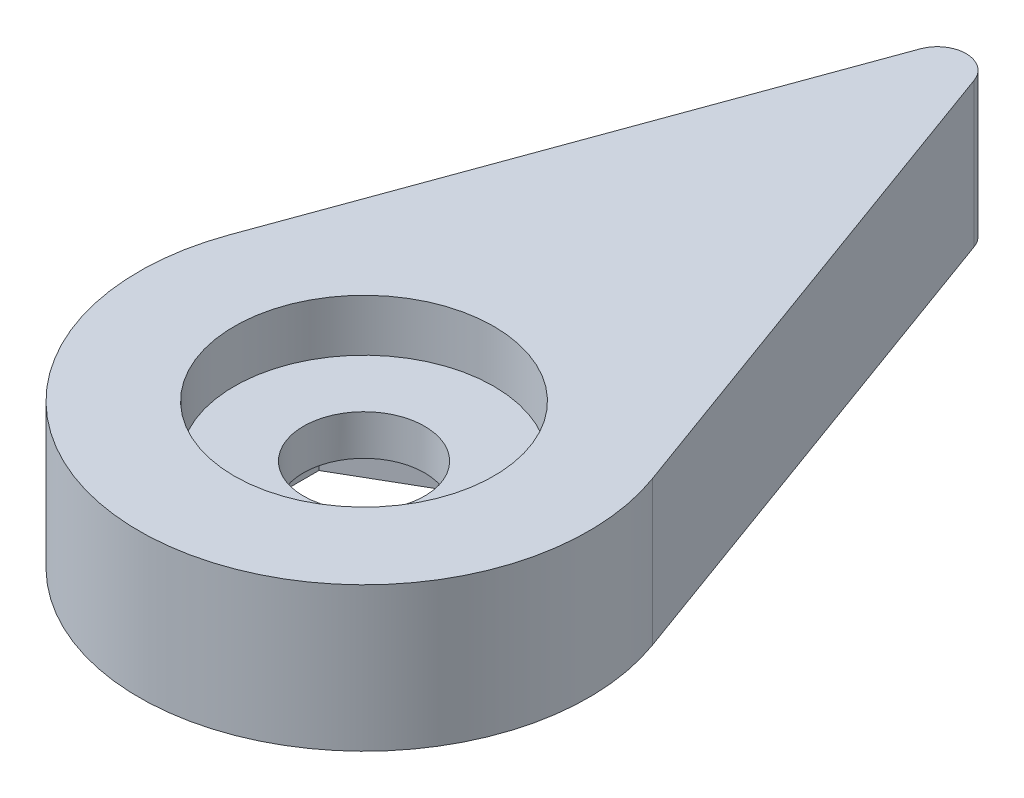
SolidWorks part; units mm, degrees
ref_plane "Front Plane" through (0, 0, 0) normal (0, 0, 1) x (1, 0, 0)
ref_plane "Top Plane" through (0, 0, 0) normal (0, 1, 0) x (1, 0, 0)
ref_plane "Right Plane" through (0, 0, 0) normal (1, 0, 0) x (0, 0, -1)
sketch "Sketch1" plane through (0, 0, 0) normal (0, 1, 0) x (1, 0, 0)
  line L3 (0, -55) -> (0, 55) construction
  line L12 (-0.9397, 20.2239) -> (-7.3296, 2.6678)
  line L15 (7.3296, 2.6678) -> (0.9397, 20.2239)
  arc A0 (-7.3296, 2.6678) -> (7.3296, 2.6678) centre (0, 0) ccw
  arc A12 (0.9397, 20.2239) -> (-0.9397, 20.2239) centre (0, 19.8819) ccw
  dimension "D1" = 7.8
  dimension "D3" = 1
  dimension "D5" = 40
extrude "Boss-Extrude2" add sketch "Sketch1" along normal blind 5
sketch "Sketch3" plane through (0, 5, 0) normal (0, 1, 0) x (1, 0, 0)
  circle A0 centre (0, 0) radius 2.1
  dimension "D1" = 4.2
extrude "Cut-Extrude1" cut sketch "Sketch3" against normal up to next
sketch "Sketch4" plane through (0, 5, 0) normal (0, 1, 0) x (1, 0, 0)
  circle A1 centre (0, 0) radius 4.5
  dimension "D1" = 9
extrude "Cut-Extrude2" cut sketch "Sketch4" against normal blind 1.8
sketch "Sketch5" plane through (0, 0, 0) normal (0, -1, 0) x (1, 0, 0)
  line L0 (0, -2.75) -> (0, 2.75) construction
  line L1 (0, 4.2724) -> (-3.7, 2.1362)
  line L2 (-3.7, 2.1362) -> (-3.7, -2.1362)
  line L3 (-3.7, -2.1362) -> (0, -4.2724)
  line L4 (0, -4.2724) -> (3.7, -2.1362)
  line L5 (3.7, -2.1362) -> (3.7, 2.1362)
  line L6 (3.7, 2.1362) -> (0, 4.2724)
  circle A0 centre (0, 0) radius 3.7 construction
  point P1 (0, 4.2724)
  dimension "D1" = 7.4
extrude "Cut-Extrude3" cut sketch "Sketch5" against normal blind 1.8
